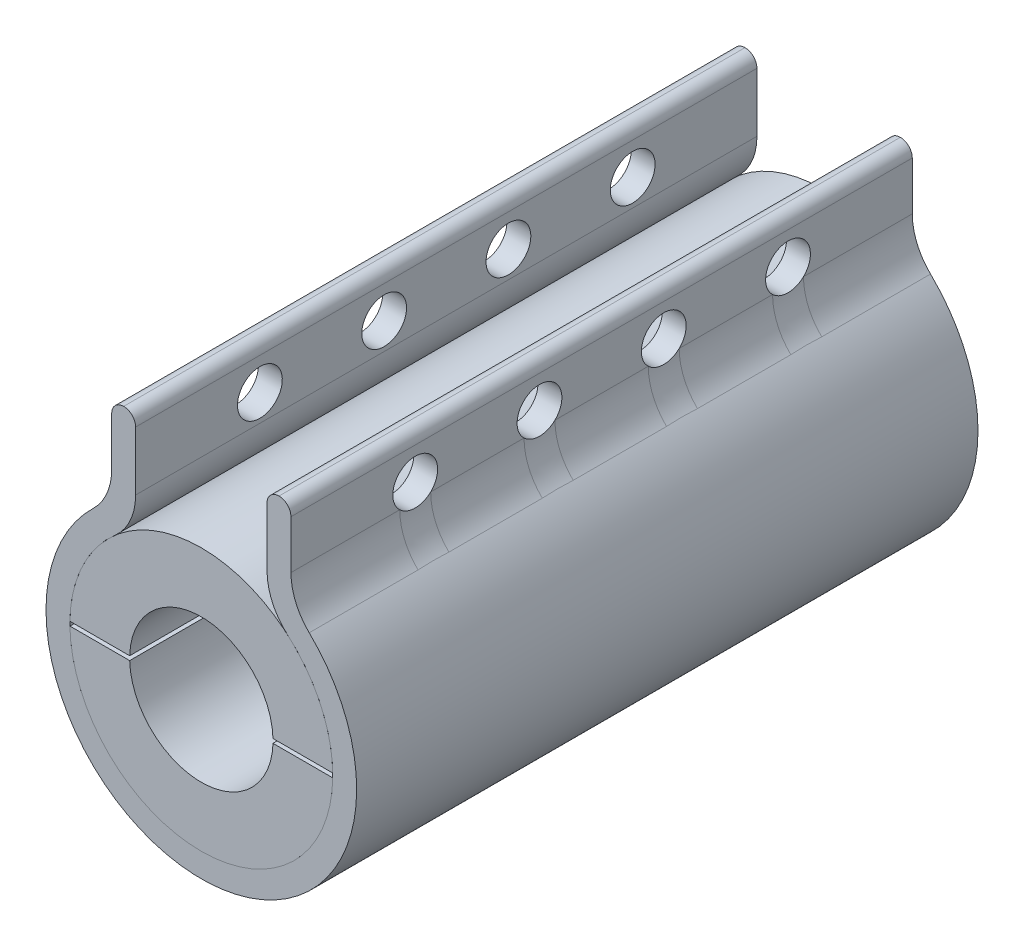
SolidWorks part; units mm, degrees
other "clamp sleeve"
other "part2"
other "part1"
ref_plane "Front Plane" through (0, 0, 0) normal (0, 0, 1) x (1, 0, 0)
ref_plane "Top Plane" through (0, 0, 0) normal (0, 1, 0) x (1, 0, 0)
ref_plane "Right Plane" through (0, 0, 0) normal (1, 0, 0) x (0, 0, -1)
sketch "Sketch1" plane through (0, 0, 0) normal (0, 0, 1) x (1, 0, 0)
  circle A0 centre (0, 0) radius 9.25
  circle A1 centre (0, 0) radius 11
  dimension "D1" = 18.5
  dimension "D2" = 22
extrude "Boss-Extrude1" add sketch "Sketch1" along normal blind 7
sketch "Sketch2" plane through (0, 0, 7) normal (0, 0, 1) x (1, 0, 0)
  circle A0 centre (0, 0) radius 11
  circle A2 centre (0, 0) radius 11 construction
  circle A3 centre (0, 0) radius 9.75
  circle A4 centre (0, 0) radius 11
  circle M5 centre (0, 0) radius 11
  dimension "D1" = 19.5
extrude "Boss-Extrude2" add sketch "Sketch2" along normal blind 17 contours A3 M5 region at (-10.6889, 0, 7)
sketch "Sketch3" plane through (0, 0, 24) normal (0, 0, 1) x (1, 0, 0)
  circle A0 centre (0, 0) radius 5.75
  circle A1 centre (0, 0) radius 11
  circle A2 centre (0, 0) radius 11 construction
  dimension "D1" = 11.5
extrude "Boss-Extrude3" add sketch "Sketch3" along normal blind 12
sketch "Sketch4" plane through (0, 0, 36) normal (0, 0, 1) x (1, 0, 0)
  line L0 (0, 0) -> (-15.6871, 0) construction
  line L2 (-8.0829, 0) -> (-4.0415, -7)
  line L3 (-4.0415, -7) -> (4.0415, -7)
  line L4 (4.0415, -7) -> (8.0829, 0)
  line L5 (8.0829, 0) -> (4.0415, 7)
  line L6 (4.0415, 7) -> (-4.0415, 7)
  line L7 (-4.0415, 7) -> (-8.0829, 0)
  circle A0 centre (0, 0) radius 7 construction
  circle A1 centre (0, 0) radius 11
  circle A2 centre (0, 0) radius 11 construction
  dimension "D1" = 7
extrude "Boss-Extrude4" add sketch "Sketch4" along normal blind 6
sketch "Sketch5" plane through (0, 0, 42) normal (0, 0, 1) x (1, 0, 0)
  circle A0 centre (0, 0) radius 6
  circle A1 centre (0, 0) radius 11
  circle A2 centre (0, 0) radius 11 construction
  dimension "D1" = 12
extrude "Boss-Extrude5" add sketch "Sketch5" along normal blind 10
sketch "Sketch16" plane through (0, 0, 0) normal (0, 0, -1) x (-1, 0, 0)
  line L1 (-12.9742, 0.175) -> (13.3052, 0.175)
  line L2 (-12.9742, 0.175) -> (-12.9742, -0.175)
  line L3 (-12.9742, -0.175) -> (13.3052, -0.175)
  line L4 (13.3052, 0.175) -> (13.3052, -0.175)
  point P4 (13.3052, 0)
  dimension "D1" = 0.35
extrude "Cut-Extrude1" cut sketch "Sketch16" against normal up to surface (52 mm away) up to face at (11, 0, 52)
sketch "Sketch17" plane through (0, 0, 52) normal (0, 0, 1) x (1, 0, 0)
  circle A0 centre (0, 0) radius 11
  arc A2 (10.9995, 0.1) -> (-10.9995, 0.1) centre (0, 0) ccw construction
  circle A3 centre (0, 0) radius 13
  dimension "D1" = 2
extrude "Boss-Extrude6" add sketch "Sketch17" against normal up to surface (52 mm away) separate body up to face at (0, -5.15, 0)
sketch "Sketch21" plane through (0, 0, 52) normal (0, 0, 1) x (1, 0, 0)
  line L0 (0, 0) -> (0, 25.8937) construction
  line L1 (5.5, 9.5263) -> (7.5, 9.5263)
  line L2 (-5.5, 18) -> (-7.5, 18)
  line L3 (-5.5, 18) -> (-5.5, 9.5263)
  line L4 (-5.5, 9.5263) -> (-7.5, 9.5263)
  line L5 (-7.5, 18) -> (-7.5, 9.5263)
  line L6 (7.5, 18) -> (7.5, 9.5263)
  line L7 (5.5, 18) -> (7.5, 18)
  line L8 (5.5, 18) -> (5.5, 9.5263)
  circle A0 centre (0, 0) radius 11 construction
  point P7 (0, 0)
  dimension "D3" = 5.5
  dimension "D1" = 2
  dimension "D2" = 18
extrude "Boss-Extrude7" add sketch "Sketch21" against normal up to surface (52 mm away) contours L3 L2 L5 L4 | L1 L6 L7 L8 up to face at (13, 0, 0)
sketch "Sketch22" plane through (0, 0, 52) normal (0, 0, 1) x (1, 0, 0)
  line L0 (5.5, 18) -> (5.5, 11.7792) construction
  line L1 (-5.5, 18) -> (5.5, 18)
  line L2 (-5.5, 18) -> (-5.5, 9.5263)
  line L3 (-5.5, 9.5263) -> (5.5, 9.5263)
  line L4 (5.5, 18) -> (5.5, 9.5263)
  circle A0 centre (0, 0) radius 11 construction
  point P7 (0, 0)
extrude "Cut-Extrude3" cut sketch "Sketch22" against normal up to surface (52 mm away) up to face at (0, 11.7997, 0)
sketch "Sketch23" plane through (7.5, 0, 0) normal (1, 0, 0) x (0, 0, -1)
  line L0 (0, 10.6184) -> (0, 18) construction
  circle A0 centre (-41.6, 14.3092) radius 1.875
  circle A1 centre (-31.2, 14.3092) radius 1.875
  circle A2 centre (-10.4, 14.3092) radius 1.875
  circle A3 centre (-20.8, 14.3092) radius 1.875
  point P10 (0, 14.3092)
  dimension "D1" = 3.75
  dimension "D2" = 10.4
  dimension "D3" = 10.4
  dimension "D4" = 10.4
  dimension "D5" = 10.4
extrude "Cut-Extrude4" cut sketch "Sketch23" against normal up to surface (15 mm away) contours A2 | A3 | A1 | A0 up to face at (-7.5, 14.3092, 26)
fillet "Fillet1" radius 1 4 edges at (7.5, 18, 26) (-7.5, 18, 26) (-5.5, 18, 26) (5.5, 18, 26)
fillet "Fillet2" radius 5 2 edges at (-7.5, 10.6184, 26) (7.5, 10.6184, 26)
fillet "Fillet3" radius 5 2 edges at (5.5, 9.5263, 26) (-5.5, 9.5263, 26)
